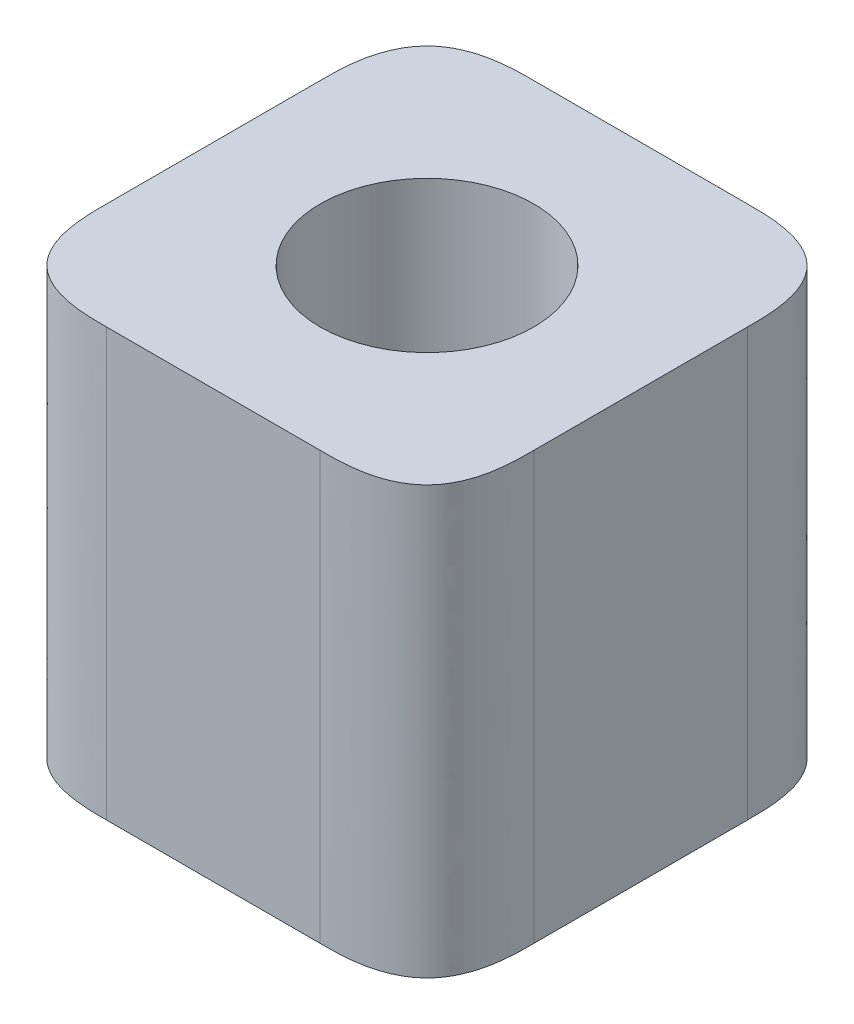
SolidWorks part; units mm, degrees
ref_plane "Front Plane" through (0, 0, 0) normal (0, 0, 1) x (1, 0, 0)
ref_plane "Top Plane" through (0, 0, 0) normal (0, 1, 0) x (1, 0, 0)
ref_plane "Right Plane" through (0, 0, 0) normal (1, 0, 0) x (0, 0, -1)
sketch "Sketch2" plane through (0, 0, 0) normal (0, 1, 0) x (1, 0, 0)
  line L0 (-5.3774, 2) -> (4.3662, 2) construction
  line L1 (-4, -4) -> (4, -4)
  line L2 (-4, -4) -> (-4, 4)
  line L3 (-4, 4) -> (4, 4)
  line L4 (4, -4) -> (4, 4)
  line L5 (-4, -4) -> (4, 4) construction
  line L6 (-4, 4) -> (4, -4) construction
  circle A0 centre (0, 0) radius 2
  dimension "D1" = 4
  dimension "D2" = 2
extrude "Boss-Extrude1" add sketch "Sketch2" along normal blind 7
sketch "Sketch3" plane through (0, 0, 0) normal (0, -1, 0) x (1, 0, 0)
  line L1 (-4, 4) -> (4, 4)
  line L2 (-4, 4) -> (-4, -4)
  line L3 (-4, -4) -> (4, -4)
  line L4 (4, 4) -> (4, -4)
extrude "Boss-Extrude2" add sketch "Sketch3" along normal blind 1
fillet "Fillet1" radius 2 4 edges at (4, 3, 4) (-4, 3, 4) (-4, 3, -4) (4, 3, -4) curvature continuous yes
